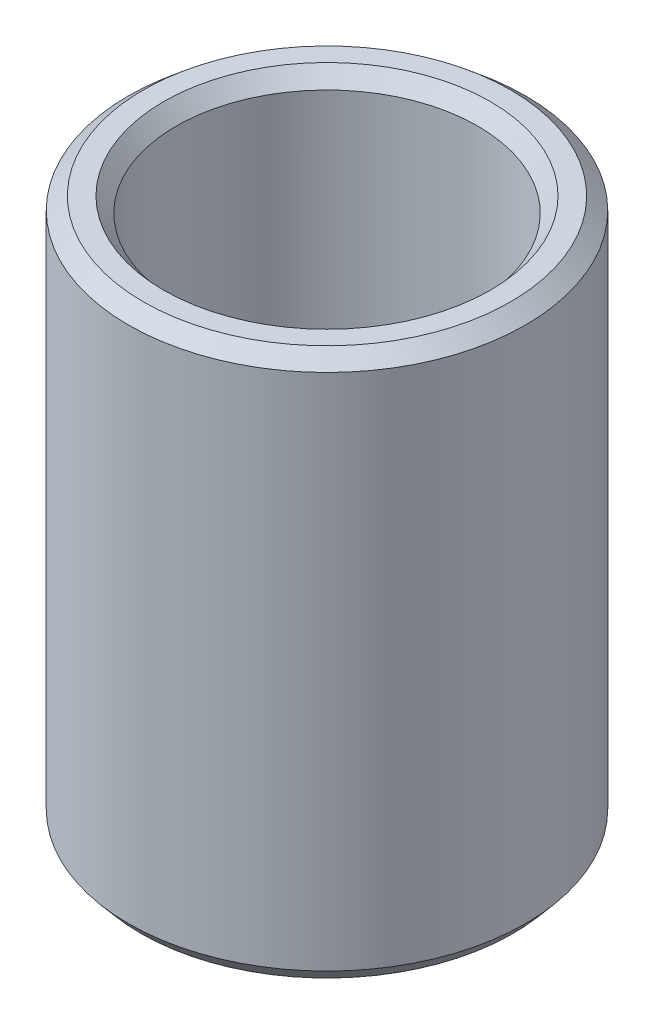
SolidWorks part; units mm, degrees
ref_plane "Front Plane" through (0, 0, 0) normal (0, 0, 1) x (1, 0, 0)
ref_plane "Top Plane" through (0, 0, 0) normal (0, 1, 0) x (1, 0, 0)
ref_plane "Right Plane" through (0, 0, 0) normal (1, 0, 0) x (0, 0, -1)
sketch "Sketch1" plane through (0, 0, 0) normal (0, 1, 0) x (1, 0, 0)
  circle A0 centre (0, 0) radius 27.5
  dimension "SLEEVE_OD" = 55
extrude "Boss-Extrude1" add sketch "Sketch1" along normal blind 75.6233
sketch "Sketch2" plane through (0, 0, 0) normal (0, 1, 0) x (1, 0, 0)
  circle A0 centre (0, 0) radius 20.8883
  dimension "BORE_D" = 41.7766
extrude "Cut-Extrude1" cut sketch "Sketch2" along normal through all
chamfer "Chamfer1" distance 1.7433 angle 49.856 4 edges at (0, 75.6233, 20.8883) (0, 0, 20.8883) (0, 0, 27.5) (0, 75.6233, 27.5) first distance on face at (0, 75.6233, 20.8883) first distance on face at (0, 0, 20.8883) first distance on face at (0, 75.6233, 27.5)
